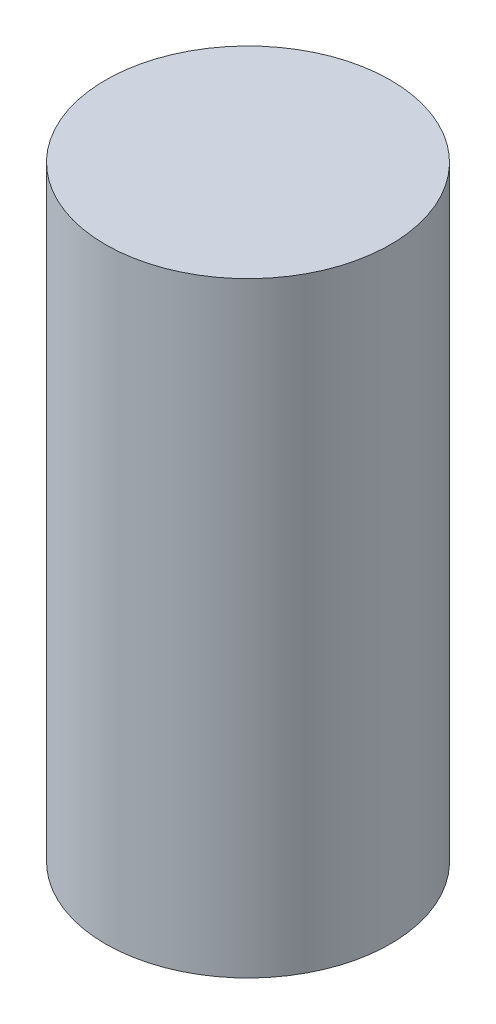
SolidWorks part; units mm, degrees
ref_plane "Front Plane" through (0, 0, 0) normal (0, 0, 1) x (1, 0, 0)
ref_plane "Top Plane" through (0, 0, 0) normal (0, 1, 0) x (1, 0, 0)
ref_plane "Right Plane" through (0, 0, 0) normal (1, 0, 0) x (0, 0, -1)
sketch "Sketch1" plane through (0, 0, 0) normal (0, 1, 0) x (1, 0, 0)
  circle A0 centre (0, 0) radius 1
  dimension "D1" = 2
extrude "Boss-Extrude1" add sketch "Sketch1" along normal blind 4.25
